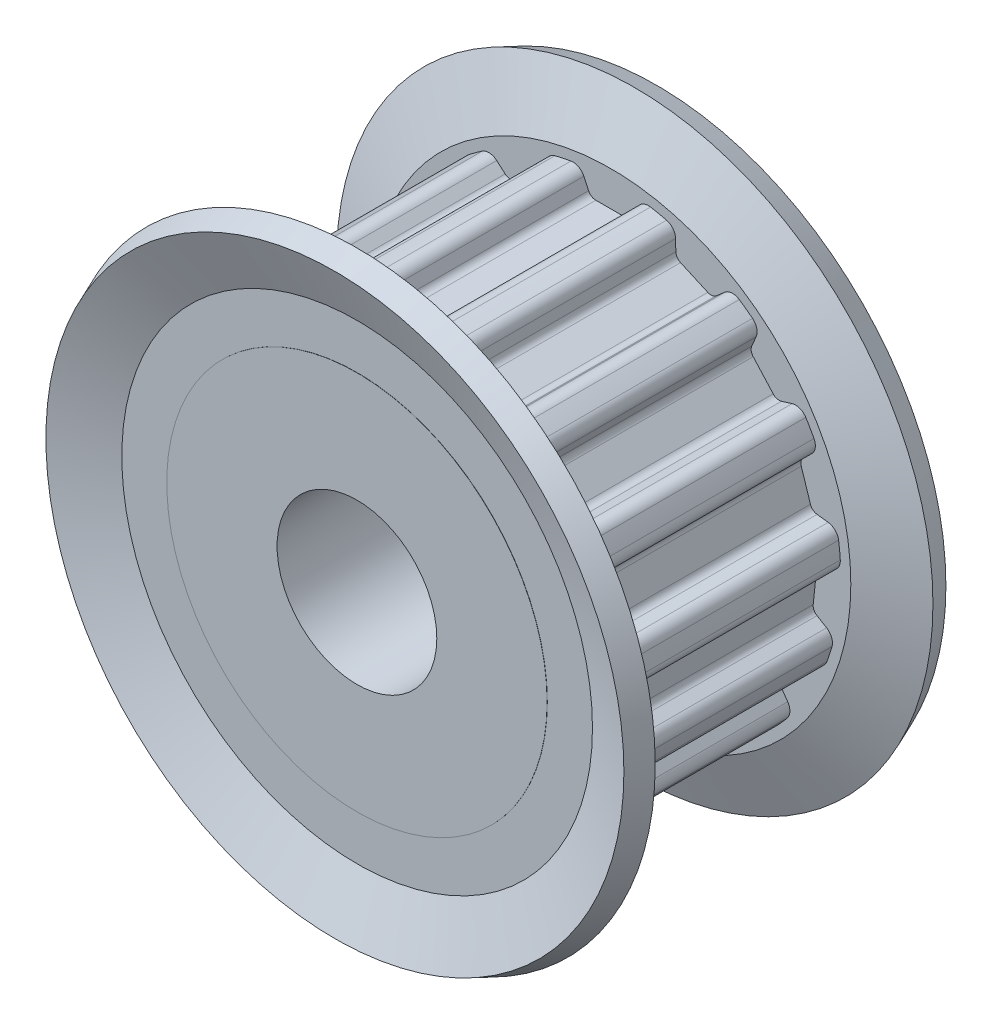
SolidWorks part; units mm, degrees
ref_plane "Front Plane" through (0, 0, 0) normal (0, 0, 1) x (1, 0, 0)
ref_plane "Top Plane" through (0, 0, 0) normal (0, 1, 0) x (1, 0, 0)
ref_plane "Right Plane" through (0, 0, 0) normal (1, 0, 0) x (0, 0, -1)
ref_axis "Axis1" through (0, 0, 75.1227) along (0, 0, -1)
sketch "SketchRevolveGearBelt01" plane through (0, 0, 0) normal (1, 0, 0) x (0, 0, -1)
  line L0 (0, 0) -> (1, 0) construction
  line L1 (6.96, 0) -> (6.96, 9.525)
  line L2 (6.96, 9.525) -> (6.95, 9.525)
  line L3 (6.95, 9.525) -> (6.95, 11.7863)
  line L4 (6.95, 11.7863) -> (8.0633, 14.4741)
  line L5 (8.0633, 14.4741) -> (6.9547, 14.9333)
  line L6 (6.9547, 14.9333) -> (5.75, 12.025)
  line L7 (5.75, 12.025) -> (5.75, 11.525)
  line L8 (5.75, 11.525) -> (-5.75, 11.525)
  line L9 (-5.75, 11.525) -> (-5.75, 12.025)
  line L10 (-5.75, 12.025) -> (-6.9547, 14.9333)
  line L11 (-6.9547, 14.9333) -> (-8.0633, 14.4741)
  line L12 (-8.0633, 14.4741) -> (-6.95, 11.7863)
  line L13 (-6.95, 11.7863) -> (-6.95, 9.525)
  line L14 (-6.95, 9.525) -> (-6.96, 9.525)
  line L15 (-6.96, 9.525) -> (-6.96, 0)
  line L16 (-6.96, 0) -> (6.96, 0)
  dimension "GearBeltSide1" = 6.96
  dimension "GearBeltFlange1OutsideWidth" = 6.95
  dimension "GearBeltFlange1OutsideLength" = 2.2613
  dimension "GearBeltFlange1X" = 1.1133
  dimension "GearBeltFlange1Y" = 2.6878
  dimension "GearBeltFlangeThickness" = 1.2
  dimension "GearBeltToothWidth1" = 5.75
  dimension "GearBeltFlangeInside" = 0.5
  dimension "GearBeltOutsideDiameter" = 11.525
  dimension "GearBeltToothWidth2" = 5.75
  dimension "GearBeltFlange2X" = 1.1133
  dimension "GearBeltFlange2OutsideWidth" = 6.95
revolve "GearBelt01" add sketch "SketchRevolveGearBelt01" angle 360 about L0
sketch "SketchToothGearBelt01" plane through (0, 0, 0) normal (0, 0, 1) x (1, 0, 0)
  line L0 (-1.3466, 11.0138) -> (-1.1098, 10.506)
  line L1 (-0.7473, 10.275) -> (0.7473, 10.275)
  line L2 (1.1098, 10.506) -> (1.3466, 11.0138)
  line L3 (1.9942, 11.3512) -> (0, 13.8912)
  line L4 (0, 13.8912) -> (-1.9942, 11.3512)
  arc A0 (-1.9942, 11.3512) -> (-1.3466, 11.0138) centre (-1.8904, 10.7602) cw
  arc A1 (-1.1098, 10.506) -> (-0.7473, 10.275) centre (-0.7473, 10.675) ccw
  arc A2 (0.7473, 10.275) -> (1.1098, 10.506) centre (0.7473, 10.675) ccw
  arc A3 (1.3466, 11.0138) -> (1.9942, 11.3512) centre (1.8904, 10.7602) cw
  dimension "GearBeltToothR1" = 1.2
  dimension "GearBeltToothR2" = 0.8
  dimension "GearBeltToothX1" = 0.2368
  dimension "GearBeltToothY1" = 0.5078
  dimension "GearBeltToothRootX" = 10.275
  dimension "GearBeltToothRootY" = 10.275
  dimension "GearBeltToothX2" = 0.2368
  dimension "GearBeltToothY2" = 0.5078
  dimension "GearBeltToothCapX1" = 1.9942
  dimension "GearBeltToothCapY1" = 2.54
  dimension "GearBeltToothCapX2" = 1.9942
  dimension "GearBeltToothCapY2" = 2.54
extrude "ToothExtrudeCutGearBelt01" cut sketch "SketchToothGearBelt01" against normal blind 5.75 and the other way blind 5.75
pattern_circular "PatternGearBelt01" count 15 every 24 about axis through (0, 0, 75.1227) along (0, 0, -1) of "ToothExtrudeCutGearBelt01"
sketch "BoreRevolveSketch" plane through (0, 0, 0) normal (1, 0, 0) x (0, 0, -1)
  line L0 (0, 0) -> (1, 0) construction
  line L1 (-6.96, 0) -> (6.96, 0)
  line L2 (6.96, 0) -> (6.96, 4)
  line L3 (6.96, 4) -> (-6.96, 4)
  line L4 (-6.96, 4) -> (-6.96, 0)
  dimension "BoreSide1" = 6.96
  dimension "TaperSide1" = 4
  dimension "BoreSide2" = 6.96
  dimension "TaperSide2" = 4
revolve "BoreRevolveCut" cut sketch "BoreRevolveSketch" angle 360 about L0
sketch "AuxiliarySketchGearBelt01" plane through (0, 0, 0) normal (0, 0, 1) x (1, 0, 0)
  circle A0 centre (0, 0) radius 12.025 construction
  dimension "PitchDiameter" = 24.05
